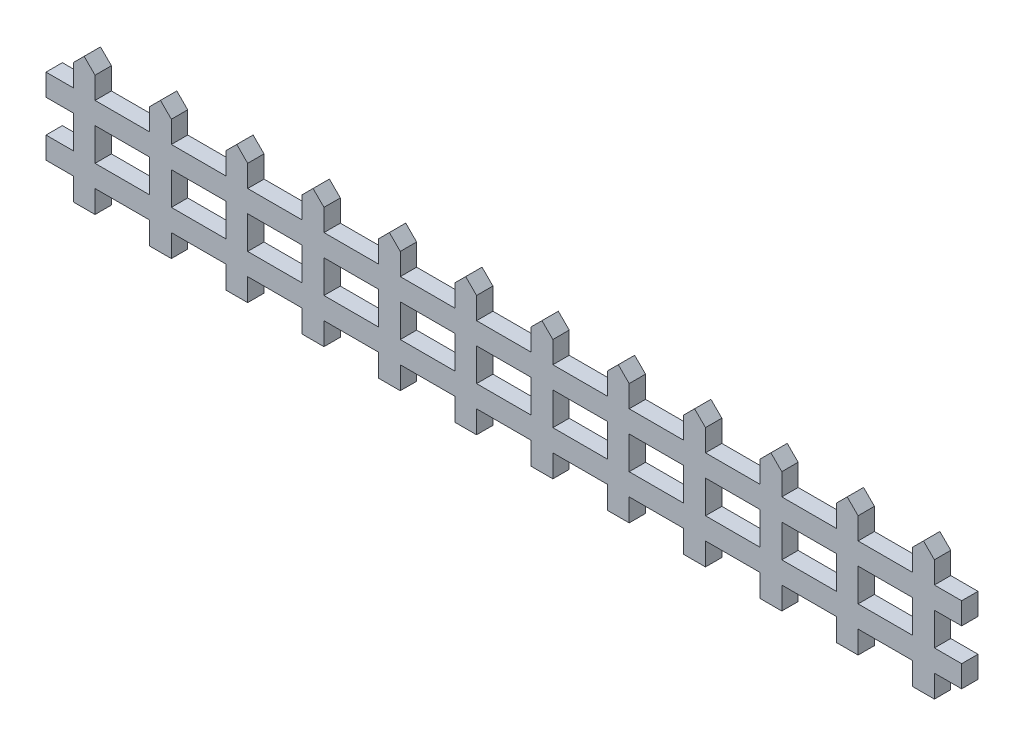
SolidWorks part; units mm, degrees
ref_plane "Front Plane" through (0, 0, 0) normal (1, 0, 0) x (0, 1, 0)
ref_plane "Top Plane" through (0, 0, 0) normal (0, 0, 1) x (0, 1, 0)
ref_plane "Right Plane" through (0, 0, 0) normal (0, 1, 0) x (-1, 0, 0)
sketch "Sketch1" plane through (0, 0, 0) normal (0, 0, 1) x (0, 1, 0)
  line L0 (-105, 74) -> (105, -74) construction
  line L1 (-105, 74) -> (105, 74) construction
  line L2 (-105, 74) -> (-105, -74) construction
  line L3 (-105, -74) -> (105, -74) construction
  line L4 (105, 74) -> (105, 63.1122) construction
  line L5 (84.9915, 53.1122) -> (82.9915, 53.1122)
  line L6 (100.9915, 67.1122) -> (98.9915, 67.1122)
  line L8 (100.9915, 63.1122) -> (98.9915, 63.1122)
  line L10 (94.9915, 72.1122) -> (98.9915, 72.1122)
  line L11 (94.9915, 72.1122) -> (94.9915, 67.1122)
  line L12 (94.9915, 44.1122) -> (98.9915, 44.1122)
  line L13 (98.9915, 72.1122) -> (98.9915, 67.1122)
  line L14 (88.9915, 72.1122) -> (84.9915, 72.1122)
  line L15 (88.9915, 72.1122) -> (88.9915, 67.1122)
  line L16 (88.9915, 44.1122) -> (84.9915, 44.1122)
  line L17 (84.9915, 72.1122) -> (84.9915, 67.1122)
  line L18 (100.9915, 53.1122) -> (98.9915, 53.1122)
  line L20 (100.9915, 49.1122) -> (98.9915, 49.1122)
  line L22 (84.9915, 49.1122) -> (82.9915, 49.1122)
  line L23 (88.9915, 49.1122) -> (88.9915, 44.1122)
  line L24 (98.9915, 49.1122) -> (98.9915, 44.1122)
  line L25 (94.9915, 49.1122) -> (94.9915, 44.1122)
  line L26 (84.9915, 49.1122) -> (84.9915, 44.1122)
  line L27 (94.9915, 53.1122) -> (88.9915, 53.1122)
  line L28 (94.9915, 63.1122) -> (88.9915, 63.1122)
  line L29 (94.9915, 63.1122) -> (94.9915, 53.1122)
  line L30 (98.9915, 63.1122) -> (98.9915, 53.1122)
  line L31 (88.9915, 63.1122) -> (88.9915, 53.1122)
  line L32 (84.9915, 63.1122) -> (84.9915, 53.1122)
  line L33 (84.9915, 63.1122) -> (82.9915, 63.1122)
  line L34 (84.9915, 67.1122) -> (82.9915, 67.1122)
  line L35 (94.9915, 67.1122) -> (88.9915, 67.1122)
  line L36 (94.9915, 49.1122) -> (88.9915, 49.1122)
  line L37 (105, 53.1122) -> (105, 49.1122)
  line L38 (100.9915, 67.1122) -> (105, 67.1122)
  line L40 (100.9915, 49.1122) -> (105, 49.1122)
  line L41 (105, 67.1122) -> (105, 63.1122)
  line L42 (82.9915, 67.1122) -> (80.8574, 67.1122)
  line L44 (82.9915, 49.1122) -> (80.8574, 49.1122)
  line L45 (80.8574, 67.1122) -> (80.8574, 63.1122)
  line L46 (82.9915, 63.1122) -> (80.8574, 63.1122)
  line L48 (82.9915, 53.1122) -> (80.8574, 53.1122)
  line L50 (100.9915, 53.1122) -> (105, 53.1122)
  line L52 (100.9915, 63.1122) -> (105, 63.1122)
  line L54 (105, 53.1122) -> (105, -74) construction
  line L56 (80.8574, 53.1122) -> (80.8574, 49.1122)
  dimension "D1" = 210
  dimension "D2" = 148
  dimension "D3" = 10
  dimension "D4" = 4
  dimension "D5" = 5
  dimension "D6" = 6
  dimension "D7" = 4
extrude "Boss-Extrude1" add sketch "Sketch1" along normal blind 3
chamfer "Chamfer1" distance 2 angle 45 4 edges at (-49.1122, 105, 1.5) (-53.1122, 105, 1.5) (-63.1122, 105, 1.5) (-67.1122, 105, 1.5)
pattern_linear "LPattern1" count 6 spacing 28 along (1, 0, 0) of "Chamfer1", "Boss-Extrude1"
